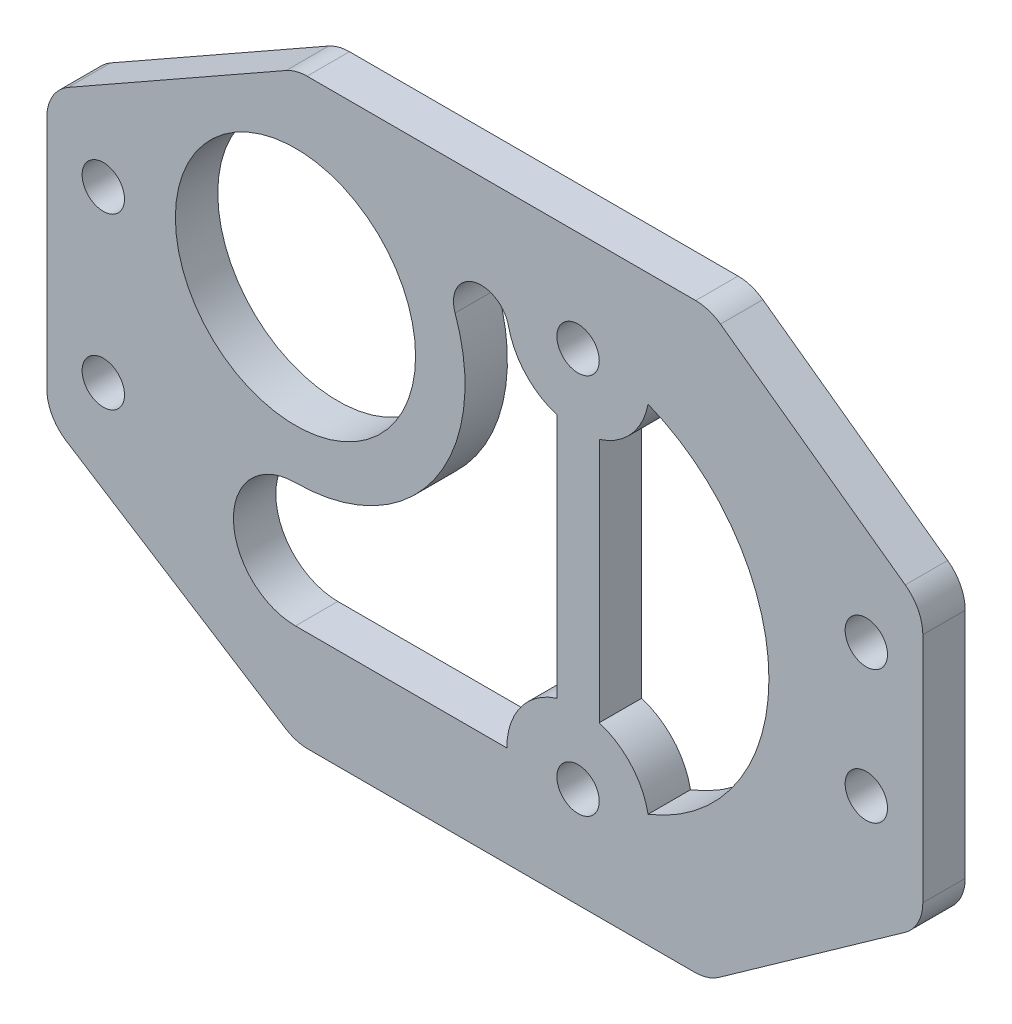
SolidWorks part; units mm, degrees
ref_plane "Front Plane" through (0, 0, 0) normal (0, 0, 1) x (1, 0, 0)
ref_plane "Top Plane" through (0, 0, 0) normal (0, 1, 0) x (1, 0, 0)
ref_plane "Right Plane" through (0, 0, 0) normal (1, 0, 0) x (0, 0, -1)
sketch "Sketch1" plane through (0, 0, 0) normal (0, 0, 1) x (1, 0, 0)
  line L0 (0, 1.648) -> (0, 18.258)
  line L1 (1.52, 20.8675) -> (16.9423, 29.6143)
  line L2 (18.4223, 30.0048) -> (45.9223, 30.0048)
  line L3 (47.6787, 29.4368) -> (60.7565, 19.9918)
  line L4 (62, 17.5597) -> (62, 1.1297)
  line L5 (60.736, -1.317) -> (47.5794, -10.6519)
  line L6 (45.8434, -11.2052) -> (18.5034, -11.2052)
  line L7 (16.8942, -10.7371) -> (1.3908, -0.8839)
  line L8 (1.3029, 16.0075) -> (6.6971, 16.0075) construction
  line L9 (0.2452, 4.0075) -> (7.7548, 4.0075) construction
  line L10 (17.6, 31.521) -> (17.6, -5.7675) construction
  line L11 (7.7548, 16.6798) -> (25.5136, 16.6798) construction
  line L12 (-39.3225, 9.3998) -> (106.4512, 9.3998) construction
  line L13 (39.1, 0.714) -> (39.1, 18.0856)
  line L14 (36.1, 18.0856) -> (36.1, 0.714)
  line L15 (37.6, 44.2333) -> (37.6, -14.3158) construction
  line L16 (32.5576, -4.1002) -> (17.6, -4.1002)
  arc A0 (18.5034, -11.2052) -> (16.8942, -10.7371) centre (18.5034, -8.2052) cw
  arc A1 (47.5794, -10.6519) -> (45.8434, -11.2052) centre (45.8434, -8.2052) cw
  arc A2 (60.7565, 19.9918) -> (62, 17.5597) centre (59, 17.5597) cw
  arc A3 (62, 1.1297) -> (60.736, -1.317) centre (59, 1.1297) cw
  arc A4 (45.9223, 30.0048) -> (47.6787, 29.4368) centre (45.9223, 27.0048) cw
  arc A5 (16.9423, 29.6143) -> (18.4223, 30.0048) centre (18.4223, 27.0048) cw
  arc A6 (0, 18.258) -> (1.52, 20.8675) centre (3, 18.258) cw
  arc A7 (0, 1.648) -> (1.3908, -0.8839) centre (3, 1.648) ccw
  circle A8 centre (4, 16.0075) radius 1.5
  circle A9 centre (4, 4.0075) radius 1.5
  circle A10 centre (58, 15.0918) radius 1.5
  circle A11 centre (58, 5.6783) radius 1.5
  circle A12 centre (37.6, 22.8998) radius 1.5
  circle A13 centre (37.6, -4.1002) radius 1.5
  circle A14 centre (17.6, 16.6798) radius 8.5
  arc A15 (36.1, 0.714) -> (32.5576, -4.1002) centre (37.6, -4.1002) ccw
  arc A16 (39.1, 18.0856) -> (42.5552, 21.966) centre (37.6, 22.8998) ccw
  arc A18 (32.6759, 21.814) -> (36.1, 18.0856) centre (37.6, 22.8998) ccw
  arc A19 (42.5552, -3.1664) -> (42.5552, 21.966) centre (37.6, 9.3998) ccw
  arc A20 (42.5552, -3.1664) -> (39.1, 0.714) centre (37.6, -4.1002) ccw
  arc A21 (17.6, 4.6798) -> (17.6, -4.1002) centre (17.6, 0.2898) ccw
  arc A22 (17.6, 4.6798) -> (28.8974, 20.7256) centre (17.6, 16.6798) ccw
  arc A23 (32.6759, 21.814) -> (28.8974, 20.7256) centre (30.7521, 21.3898) ccw
  point P15 (17.6307, -11.2052)
  point P18 (46.7996, -11.2052)
  point P21 (62, 19.0936)
  point P24 (62, -0.4201)
  point P27 (46.8923, 30.0048)
  point P30 (17.6307, 30.0048)
  point P33 (0, 20.0054)
  point P36 (0, 0)
  dimension "D8" = 3
  dimension "D9" = 3
  dimension "D10" = 3
  dimension "D11" = 3
  dimension "D12" = 3
  dimension "D13" = 3
  dimension "D14" = 3
  dimension "D16" = 3
  dimension "D27" = 17
  dimension "D28" = 12
  dimension "D30" = 4.71
  dimension "D31" = 24
  dimension "D32" = 3.94
  dimension "D1" = 209.56
  dimension "D2" = 41.21
  dimension "D3" = 62
  dimension "D4" = 27.34
  dimension "D5" = 27.5
  dimension "D6" = 17.73
  dimension "D7" = 16.61
  dimension "D15" = 16.43
  dimension "D17" = 4
  dimension "D18" = 4.86
  dimension "D19" = 4.9
  dimension "D20" = 4
  dimension "D21" = 20.4
  dimension "D22" = 27
  dimension "D23" = 7.105
  dimension "D24" = 17.6
  dimension "D25" = 20.605
  dimension "D26" = 7.28
  dimension "D29" = 3
other "AlignGroup1"
extrude "Boss-Extrude1" add sketch "Sketch1" along normal blind 3
